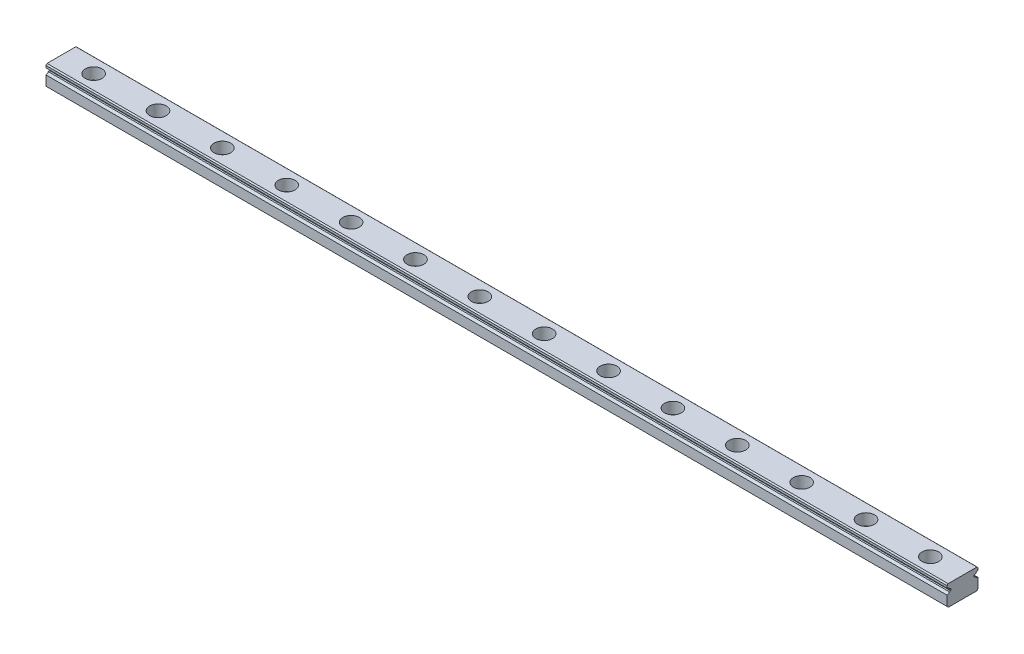
SolidWorks part; units mm, degrees
ref_plane "Front Plane" through (0, 0, 0) normal (0, 0, 1) x (1, 0, 0)
ref_plane "Top Plane" through (0, 0, 0) normal (0, 1, 0) x (1, 0, 0)
ref_plane "Right Plane" through (0, 0, 0) normal (1, 0, 0) x (0, 0, -1)
sketch "Sketch1" plane through (0, 0, 0) normal (1, 0, 0) x (0, 0, -1)
  line L0 (-6, 0.5) -> (-5.5, 0)
  line L1 (-5.5, 0) -> (5.5, 0)
  line L2 (5.5, 0) -> (6, 0.5)
  line L3 (6, 0.5) -> (6, 4.3168)
  line L4 (5.1128, 4.992) -> (4.622, 5.0785)
  line L5 (4.5, 5.217) -> (4.5, 5.783)
  line L6 (4.622, 5.9215) -> (5.1128, 6.008)
  line L7 (6, 6.6832) -> (6, 7.5)
  line L8 (5.6, 8) -> (-5.6, 8)
  line L9 (-6, 7.5) -> (-6, 6.6832)
  line L10 (-5.1128, 6.008) -> (-4.622, 5.9215)
  line L11 (-4.5, 5.783) -> (-4.5, 5.217)
  line L12 (-4.622, 5.0785) -> (-5.1128, 4.992)
  line L13 (-6, 4.3168) -> (-6, 0.5)
  arc A0 (6, 4.3168) -> (5.1128, 4.992) centre (6.2, 5.5) cw
  arc A1 (4.622, 5.0785) -> (4.5, 5.217) centre (4.853, 5.4051) cw
  arc A2 (4.5, 5.783) -> (4.622, 5.9215) centre (4.853, 5.5949) cw
  arc A3 (5.1128, 6.008) -> (6, 6.6832) centre (6.2, 5.5) cw
  arc A4 (6, 7.5) -> (5.6, 8) centre (5.0602, 7.1582) ccw
  arc A5 (-5.6, 8) -> (-6, 7.5) centre (-5.0602, 7.1582) ccw
  arc A6 (-6, 6.6832) -> (-5.1128, 6.008) centre (-6.2, 5.5) cw
  arc A7 (-4.622, 5.9215) -> (-4.5, 5.783) centre (-4.853, 5.5949) cw
  arc A8 (-4.5, 5.217) -> (-4.622, 5.0785) centre (-4.853, 5.4051) cw
  arc A9 (-5.1128, 4.992) -> (-6, 4.3168) centre (-6.2, 5.5) cw
extrude "Extrude1" add sketch "Sketch1" along normal blind 350
sketch "Sketch2" plane through (0, 0, 0) normal (0, 0, -1) x (-1, 0, 0)
  line L0 (-12.5, 8) -> (-9.25, 8)
  line L1 (-9.25, 8) -> (-9.25, 3.5)
  line L2 (-9.25, 3.5) -> (-10.75, 3.5)
  line L3 (-10.75, 3.5) -> (-10.75, 0.2)
  line L4 (-10.75, 0.2) -> (-10.55, 0)
  line L5 (-10.55, 0) -> (-12.5, 0)
  line L6 (-350, 0) -> (0, 0) construction
  line L7 (-12.5, 0) -> (-12.5, 8) construction
  line L8 (-350, 8) -> (0, 8) construction
  line L9 (0, 4.3168) -> (0, 0.5) construction
  line L10 (-12.5, 8) -> (-12.5, 0)
  dimension "D1" = 12.5
  dimension "D2" = 3.5
  dimension "D3" = 3.9
  dimension "D4" = 4.5
  dimension "D5" = 6.5
  dimension "D6" = 45
revolve "Cut-Revolve1" cut sketch "Sketch2" angle 360 about L7 reverse direction yes
sketch "Sketch3" plane through (125, 0, 0) normal (0, 0, -1) x (-1, 0, 0)
  line L0 (-212.5, 8) -> (-209.25, 8)
  line L1 (-209.25, 8) -> (-209.25, 3.5)
  line L2 (-209.25, 3.5) -> (-210.75, 3.5)
  line L3 (-210.75, 3.5) -> (-210.75, 0.2)
  line L4 (-210.75, 0.2) -> (-210.55, 0)
  line L5 (-210.55, 0) -> (-212.5, 0)
  line L6 (-225, 4.3168) -> (-225, 0.5) construction
  line L7 (-212.5, 0) -> (-212.5, 8) construction
  line L8 (-225, 0) -> (125, 0) construction
  line L9 (-225, 8) -> (125, 8) construction
  line L10 (-212.5, 8) -> (-212.5, 0)
  dimension "D1" = 3.5
  dimension "D2" = 12.5
  dimension "D3" = 3.9
  dimension "D4" = 45
  dimension "D5" = 4.5
  dimension "D6" = 6.5
revolve "Cut-Revolve2" cut sketch "Sketch3" angle 360 about L7 reverse direction yes
sketch "Sketch8" plane through (0, 0, 0) normal (1, 0, 0) x (0, 0, -1)
  circle A0 centre (3.5, -0.3) radius 0.5
extrude "Extrude2" cut sketch "Sketch8" along normal blind 150
ref_axis "Axis1" through (-7.5, 0, 0) along (1, 0, 0)
pattern_linear "LPattern1" count 13 spacing 25 along (-1, 0, 0) of "Cut-Revolve2"
